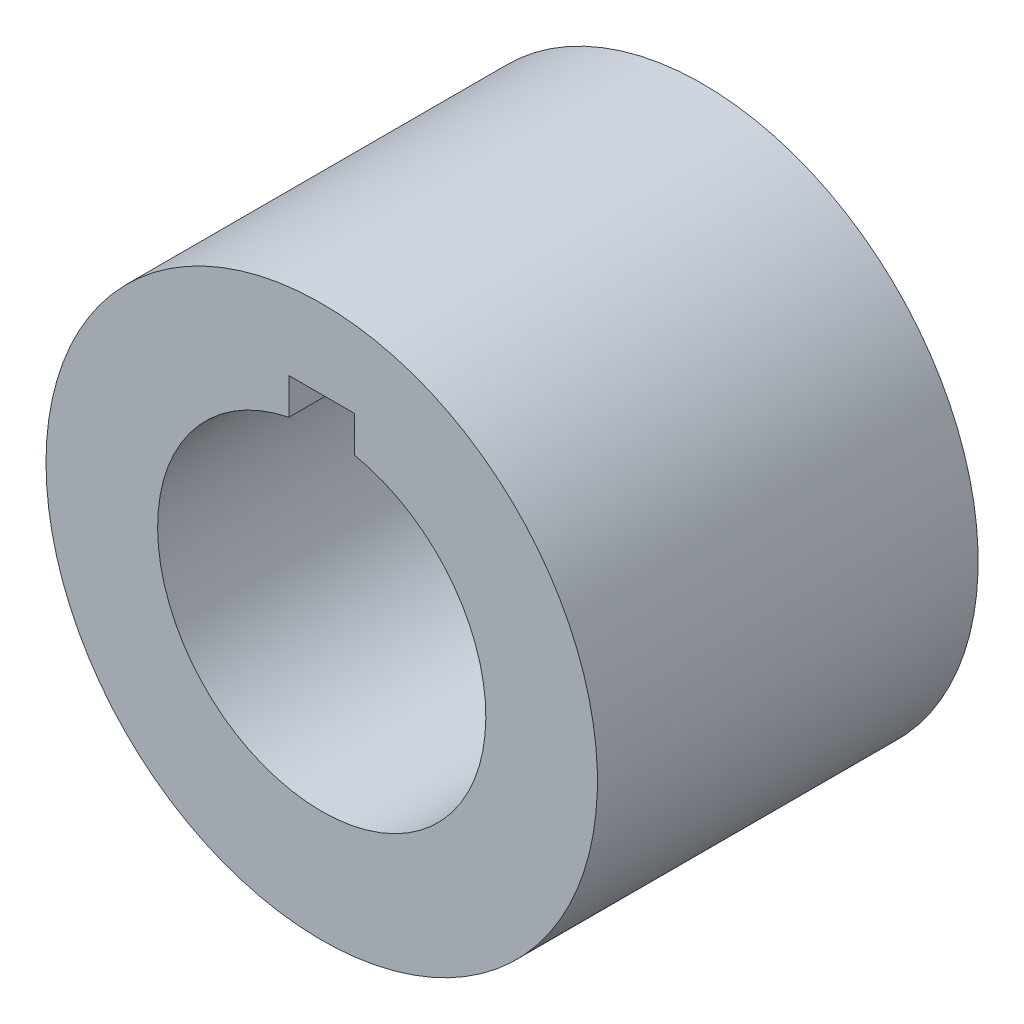
SolidWorks part; units mm, degrees
ref_plane "Front Plane" through (0, 0, 0) normal (0, 0, 1) x (1, 0, 0)
ref_plane "Top Plane" through (0, 0, 0) normal (0, 1, 0) x (1, 0, 0)
ref_plane "Right Plane" through (0, 0, 0) normal (1, 0, 0) x (0, 0, -1)
sketch "Sketch1" plane through (0, 0, 0) normal (0, 0, 1) x (1, 0, 0)
  circle A0 centre (0, 0) radius 12.5
  circle A1 centre (0, 0) radius 21
  dimension "D1" = 42
  dimension "D2" = 25
extrude "Boss-Extrude4" add sketch "Sketch1" along normal blind 29
sketch "Sketch3" plane through (0, 0, 29) normal (0, 0, 1) x (1, 0, 0)
  line L1 (-2.5, 15) -> (2.5, 15)
  line L2 (-2.5, 15) -> (-2.5, 10)
  line L3 (-2.5, 10) -> (2.5, 10)
  line L4 (2.5, 15) -> (2.5, 10)
  line L5 (-2.5, 15) -> (2.5, 10) construction
  line L6 (-2.5, 10) -> (2.5, 15) construction
  circle A0 centre (0, 0) radius 12.5 construction
  point P0 (0, 12.5)
  dimension "D1" = 5
  dimension "D2" = 5
  dimension "D3" = 5
  dimension "D4" = 2.5
extrude "Cut-Extrude3" cut sketch "Sketch3" against normal blind 25.5
fillet "Fillet5" radius 2.5 1 edges at (2.5, 13.6237, 3.5)
fillet "Fillet6" radius 2.5 1 edges at (-2.5, 13.6237, 3.5)
